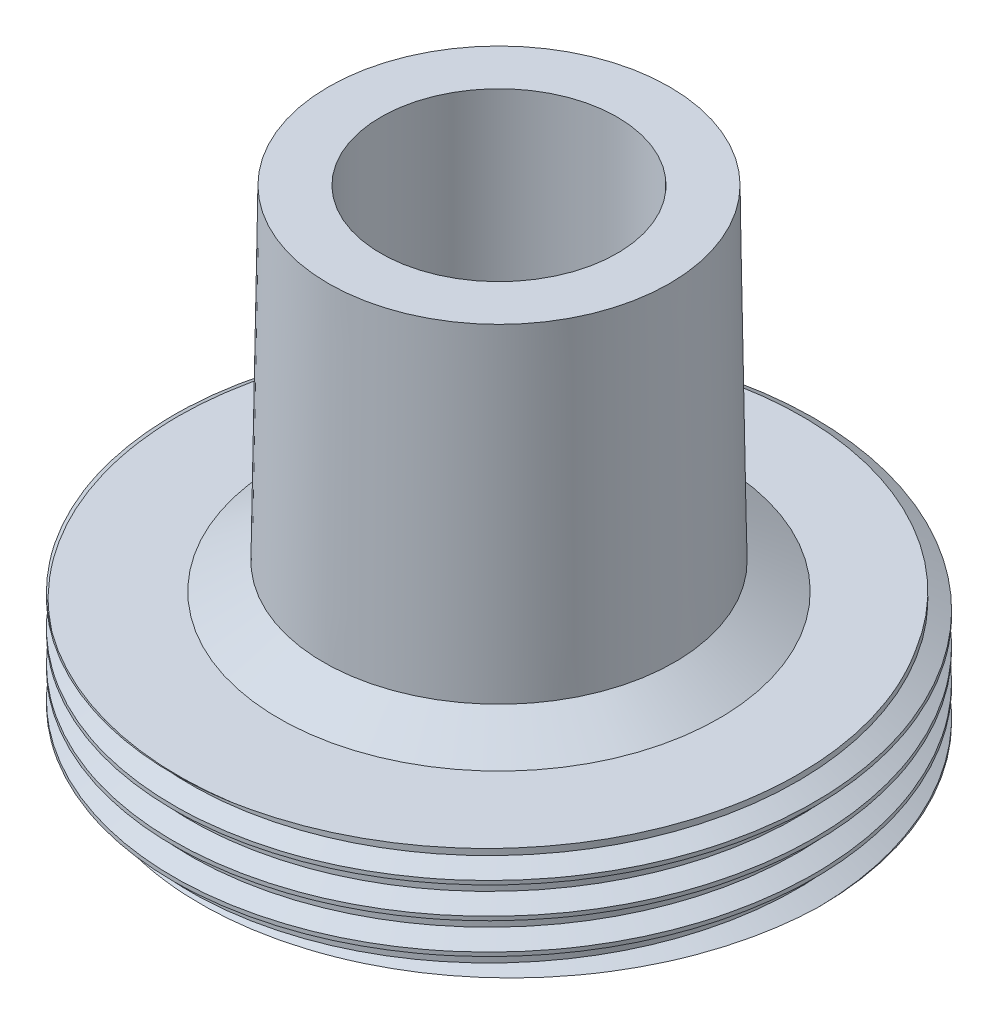
SolidWorks part; units mm, degrees
ref_plane "Front Plane" through (0, 0, 0) normal (0, 0, 1) x (1, 0, 0)
ref_plane "Top Plane" through (0, 0, 0) normal (0, 1, 0) x (1, 0, 0)
ref_plane "Right Plane" through (0, 0, 0) normal (1, 0, 0) x (0, 0, -1)
sketch "Sketch1" plane through (0, 0, 0) normal (0, 0, 1) x (1, 0, 0)
  line L0 (0, 0) -> (0, 53.092) construction
  line L1 (-20.65, 23.9851) -> (-18.35, 23.9851)
  line L2 (-18.35, 23.9851) -> (-18.35, 30.2851)
  line L3 (-20.65, 23.9851) -> (-20.65, 31.2851)
  line L6 (-11, 53.9851) -> (-7.625, 53.9851)
  line L7 (-7.625, 53.9851) -> (-7.625, 33.4851)
  line L8 (-7.625, 33.4851) -> (0, 33.4851)
  line L9 (-18.35, 30.2851) -> (-14.95, 30.2851)
  line L10 (-14.95, 30.2851) -> (-14.95, 25.7851)
  line L11 (-14.95, 25.7851) -> (-14.25, 25.7851)
  line L14 (-11.85, 31.7851) -> (0, 31.7851)
  line L15 (0, 31.7851) -> (0, 33.4851)
  line L16 (-14.25, 25.7851) -> (-11.85, 31.7851)
  line L17 (-20.65, 31.2851) -> (-14.2, 31.2851)
  line L18 (-14.2, 31.2851) -> (-11.3223, 32.9851)
  line L19 (-11.3223, 32.9851) -> (-11, 53.9851)
  dimension "D1" = 6.3
  dimension "D2" = 22
  dimension "D3" = 15.25
  dimension "D4" = 20.5
  dimension "D5" = 30
  dimension "D6" = 28.4
  dimension "D7" = 41.3
  dimension "D8" = 36.7
  dimension "D9" = 7.3
  dimension "D10" = 1.8
  dimension "D11" = 29.9
  dimension "D12" = 0.7
  dimension "D13" = 23.7
  dimension "D14" = 6
  dimension "D15" = 9
revolve "Revolve1" add sketch "Sketch1" angle 360 about L0
sketch "Sketch2" plane through (0, 31.7851, 0) normal (0, -1, 0) x (1, 0, 0)
  line L0 (0, 0) -> (0, 3.8) construction
  line L1 (1.1, 3.6373) -> (1.1, 7.3431)
  line L2 (0, 0) -> (3.8, 0) construction
  line L3 (3.6373, 1.1) -> (7.3431, 1.1)
  line L4 (0, 7.425) -> (0, 22.3636) construction
  line L5 (7.425, 0) -> (26.2688, 0) construction
  circle A2 centre (0, 0) radius 2.05
  arc A3 (3.6373, 1.1) -> (1.1, 3.6373) centre (0, 0) ccw
  arc A4 (7.3431, 1.1) -> (1.1, 7.3431) centre (0, 0) ccw
  dimension "D3" = 1.1
  dimension "D4" = 1.1
extrude "Cut-Extrude1" cut sketch "Sketch2" against normal through all both and the other way through all
pattern_circular "CirPattern1" count 4 every 90 about axis through (0, 31.7851, 0) along (0, 1, 0) of "Cut-Extrude1"
sketch "Sketch3" plane through (0, 33.4851, 0) normal (0, 1, 0) x (1, 0, 0)
  circle A0 centre (0, 0) radius 3.8
  circle A1 centre (0, 0) radius 2.05
extrude "Boss-Extrude1" add sketch "Sketch3" along normal blind 3.5
thread "Thread1" pitch 2 method cut profile "Thread Profile1" start angle 0, offset 2, length 10, pitch 2, diameter 41.3
ref_plane "Plane1" through (20.65, 21.9851, 0) normal (0, 0, 1) x (1, 0, 0)
sketch "Thread Profile1" plane through (20.65, 21.9851, 0) normal (0, 0, 1) x (1, 0, 0)
  line L0 (0, 0) -> (0, 2) construction
  line L11 (0, 0) -> (0, 1.75)
  line L12 (0, 1.75) -> (-1.0825, 1.125)
  line L13 (-1.0825, 1.125) -> (-1.0825, 0.625)
  line L15 (-1.0825, 0.625) -> (0, 0)
  line L17 (-1.0825, 0.875) -> (0, 0.875) construction
  point P2 (0, 0)
  dimension "Pitch" = 2
  dimension "Profile_Angle" = 60
  dimension "Profile_Land" = 0.5
  dimension "Profile_Height" = 1.0825
